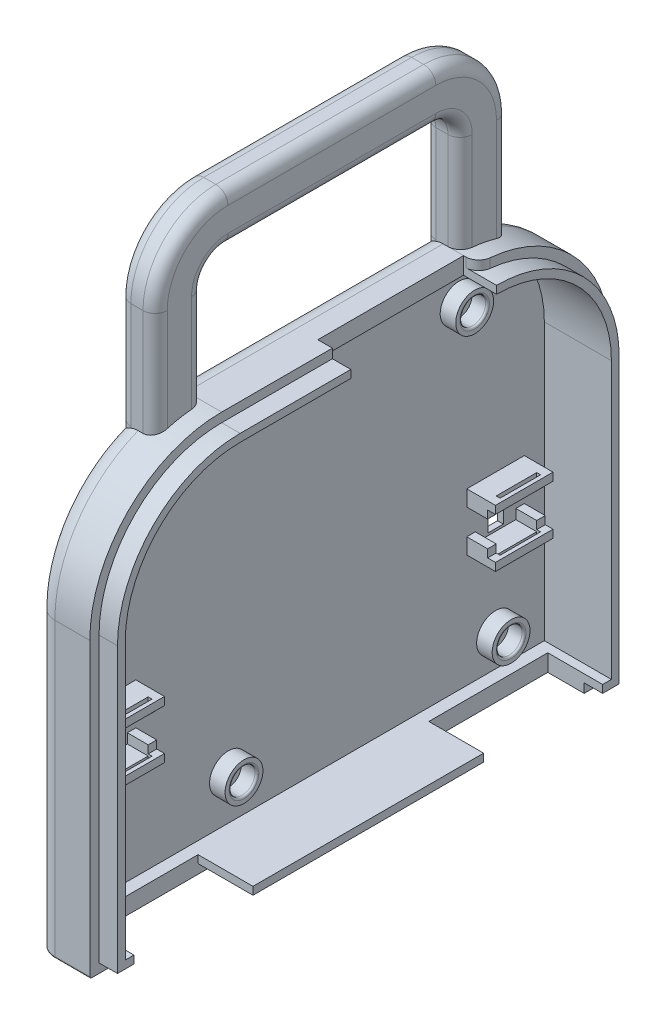
SolidWorks part; units mm, degrees
ref_plane "Front Plane" through (0, 0, 0) normal (0, 0, 1) x (1, 0, 0)
ref_plane "Top Plane" through (0, 0, 0) normal (0, 1, 0) x (1, 0, 0)
ref_plane "Right Plane" through (0, 0, 0) normal (1, 0, 0) x (0, 0, -1)
sketch "Sketch1" plane through (0, 0, 0) normal (1, 0, 0) x (0, 0, -1)
  line L0 (-52.8, 99.65) -> (52.8, 99.65)
  line L1 (-107.1, 45.35) -> (-107.1, -45.35)
  line L2 (-70, -75.35) -> (70, -75.35)
  line L3 (107.1, 45.35) -> (107.1, -45.35)
  line L4 (107.1, 0) -> (-107.1, 0) construction
  line L5 (0, 99.65) -> (0, -75.35) construction
  line L11 (107.1, -45.35) -> (107.1, -75.35)
  line L12 (107.1, -75.35) -> (70, -75.35)
  line L13 (-83.2, -1.7) -> (-76.8, -1.7)
  line L14 (-83.2, -1.7) -> (-83.2, -18.3)
  line L15 (-83.2, -18.3) -> (-76.8, -18.3)
  line L16 (-76.8, -1.7) -> (-76.8, -18.3)
  line L17 (-83.2, -1.7) -> (-76.8, -18.3) construction
  line L18 (-83.2, -18.3) -> (-76.8, -1.7) construction
  line L19 (76.8, -1.7) -> (83.2, -1.7)
  line L20 (76.8, -1.7) -> (76.8, -18.3)
  line L21 (76.8, -18.3) -> (83.2, -18.3)
  line L22 (83.2, -1.7) -> (83.2, -18.3)
  line L23 (76.8, -1.7) -> (83.2, -18.3) construction
  line L24 (76.8, -18.3) -> (83.2, -1.7) construction
  line L25 (80, -10) -> (-80, -10) construction
  line L27 (-107.1, -45.35) -> (-107.1, -75.35)
  line L28 (-107.1, -75.35) -> (-70, -75.35)
  arc A0 (52.8, 99.65) -> (107.1, 45.35) centre (52.8, 45.35) cw
  arc A1 (-52.8, 99.65) -> (-107.1, 45.35) centre (-52.8, 45.35) ccw
  point P16 (0, 0)
  point P17 (-80, -10)
  point P32 (80, -10)
  point P39 (-80, -10)
  point P40 (0, -10)
  dimension "D4" = 54.3
  dimension "D2" = 175
  dimension "D3" = 214.2
  dimension "D5" = 140
  dimension "D6" = 30
  dimension "D7" = 160
  dimension "D8" = 6.4
  dimension "D9" = 16.6
  dimension "D10" = 6.4
  dimension "D11" = 16.6
  dimension "D12" = 10
extrude "Boss-Extrude1" add sketch "Sketch1" along normal blind 2.4
sketch "Sketch9" plane through (2.4, 0, 0) normal (1, 0, 0) x (0, 0, -1)
  line L17 (52.8, 99.65) -> (-52.8, 99.65)
  line L31 (52.8, 99.65) -> (-52.8, 99.65)
  line L32 (-107.1, 45.35) -> (-107.1, -75.35)
  line L33 (-107.1, 45.35) -> (-107.1, -75.35)
  line L34 (-107.1, -75.35) -> (107.1, -75.35)
  line L39 (107.1, -75.35) -> (107.1, 45.35)
  line L43 (107.1, -75.35) -> (107.1, 45.35)
  line L45 (-107.1, -75.35) -> (107.1, -75.35)
  arc A15 (-52.8, 99.65) -> (-107.1, 45.35) centre (-52.8, 45.35) ccw
  arc A16 (-52.8, 99.65) -> (-107.1, 45.35) centre (-52.8, 45.35) ccw
  arc A17 (107.1, 45.35) -> (52.8, 99.65) centre (52.8, 45.35) ccw
  arc A18 (107.1, 45.35) -> (52.8, 99.65) centre (52.8, 45.35) ccw
  dimension "D1" = 0
sketch "Sketch10" plane through (2.4, 0, 0) normal (1, 0, 0) x (0, 0, -1)
  line L0 (65, -55.35) -> (0, -55.35) construction
  line L1 (-65, -55.35) -> (65, -55.35) construction
  line L2 (-65, -55.35) -> (-65, 54.65) construction
  line L3 (-65, 54.65) -> (65, 54.65) construction
  line L4 (65, -55.35) -> (65, 54.65) construction
  line L5 (-65, -55.35) -> (65, 54.65) construction
  line L6 (-65, 54.65) -> (65, -55.35) construction
  line L7 (0, -55.35) -> (-65, -55.35) construction
  line L8 (-107.1, -75.35) -> (107.1, -75.35) construction
  line L9 (0, -0.35) -> (0, 0) construction
  line L10 (0, -0.35) -> (0, -50.35) construction
  line L11 (-65, 54.65) -> (-65, 70.65) construction
  line L12 (-65, 70.65) -> (-70, 70.65) construction
  line L13 (0, -50.35) -> (-30, -50.35) construction
  circle A11 centre (-30, -50.35) radius 2.3
  circle A13 centre (65, 69.65) radius 2.3
  circle A14 centre (80, -55.35) radius 2.3
  circle A15 centre (-70, 70.65) radius 2.3
  point P0 (0, -0.35)
  point P11 (0, -55.35)
  point P12 (32.5, -55.35)
  point P14 (-32.5, -55.35)
  dimension "D3" = 15
  dimension "D4" = 20
  dimension "D8" = 4.6
  dimension "D1" = 130
  dimension "D2" = 110
  dimension "D5" = 50
  dimension "D6" = 15
  dimension "D7" = 16
  dimension "D9" = 5
  dimension "D10" = 30
extrude "Cut-Extrude1" cut sketch "Sketch10" against normal blind 100 and the other way blind 1000
sketch "Sketch12" plane through (2.4, 0, 0) normal (1, 0, 0) x (0, 0, -1)
  line L5 (-88.35, -18.3) -> (-88.35, -15.3)
  line L6 (-88.35, -18.3) -> (-88.35, -1.7) construction
  line L22 (71.65, -18.3) -> (71.65, -15.3)
  line L23 (71.65, -18.3) -> (71.65, -1.7) construction
  line L24 (71.65, -18.3) -> (88.35, -18.3) construction
  line L25 (88.35, -18.3) -> (88.35, -1.7) construction
  line L26 (71.65, -1.7) -> (88.35, -1.7) construction
  line L27 (71.65, -18.3) -> (88.35, -1.7) construction
  line L28 (88.35, -18.3) -> (71.65, -1.7) construction
  line L29 (71.65, -1.7) -> (71.65, -4.7)
  line L30 (88.35, -18.3) -> (88.35, -15.3)
  line L31 (88.35, -1.7) -> (88.35, -4.7)
  line L32 (71.65, -1.7) -> (88.35, -1.7) construction
  line L33 (88.35, -18.3) -> (71.65, -18.3) construction
  line L34 (88.35, -15.3) -> (91.85, -15.3)
  line L35 (71.65, -15.3) -> (68.15, -15.3)
  line L36 (68.15, -15.3) -> (68.15, -21.8)
  line L37 (68.15, -21.8) -> (91.85, -21.8)
  line L38 (91.85, -21.8) -> (91.85, -15.3)
  line L39 (71.65, -4.7) -> (68.15, -4.7)
  line L40 (68.15, -4.7) -> (68.15, 1.8)
  line L41 (68.15, 1.8) -> (91.85, 1.8)
  line L42 (91.85, 1.8) -> (91.85, -4.7)
  line L43 (91.85, -4.7) -> (88.35, -4.7)
  line L44 (83.2, -18.3) -> (76.8, -1.7) construction
  line L45 (83.2, -1.7) -> (76.8, -18.3) construction
  line L46 (-88.35, -18.3) -> (-71.65, -18.3) construction
  line L47 (-71.65, -18.3) -> (-71.65, -1.7) construction
  line L48 (-88.35, -1.7) -> (-71.65, -1.7) construction
  line L49 (-88.35, -18.3) -> (-71.65, -1.7) construction
  line L50 (-71.65, -18.3) -> (-88.35, -1.7) construction
  line L51 (-88.35, -1.7) -> (-88.35, -4.7)
  line L52 (-71.65, -18.3) -> (-71.65, -15.3)
  line L53 (-71.65, -1.7) -> (-71.65, -4.7)
  line L54 (-88.35, -1.7) -> (-71.65, -1.7) construction
  line L55 (-71.65, -18.3) -> (-88.35, -18.3) construction
  line L56 (-71.65, -15.3) -> (-68.15, -15.3)
  line L57 (-88.35, -15.3) -> (-91.85, -15.3)
  line L58 (-91.85, -15.3) -> (-91.85, -21.8)
  line L59 (-91.85, -21.8) -> (-68.15, -21.8)
  line L60 (-68.15, -21.8) -> (-68.15, -15.3)
  line L61 (-88.35, -4.7) -> (-91.85, -4.7)
  line L62 (-91.85, -4.7) -> (-91.85, 1.8)
  line L63 (-91.85, 1.8) -> (-68.15, 1.8)
  line L64 (-68.15, 1.8) -> (-68.15, -4.7)
  line L65 (-68.15, -4.7) -> (-71.65, -4.7)
  line L66 (-76.8, -18.3) -> (-83.2, -1.7) construction
  line L67 (-83.2, -18.3) -> (-76.8, -1.7) construction
  line L68 (-88.35, -1.7) -> (-88.35, -0.7047)
  line L69 (-88.35, -0.7047) -> (-71.65, -0.7047)
  line L70 (-71.65, -0.7047) -> (-71.65, -1.7)
  line L71 (-88.35, -18.3) -> (-88.35, -19.3)
  line L72 (-88.35, -19.3) -> (-71.65, -19.3)
  line L73 (-71.65, -19.3) -> (-71.65, -18.3)
  line L74 (88.35, -18.3) -> (88.35, -19.3)
  line L75 (88.35, -19.3) -> (71.65, -19.3)
  line L76 (71.65, -19.3) -> (71.65, -18.3)
  line L77 (88.35, -1.7) -> (88.35, -0.7047)
  line L78 (88.35, -0.7047) -> (71.65, -0.7047)
  line L79 (71.65, -0.7047) -> (71.65, -1.7)
  point P3 (-0.1438, 64.1533)
  point P4 (-80, -10)
  point P19 (80, -10)
  point P21 (-80, -10)
  point P30 (380.6447, 32.9453)
  point P31 (130.7088, -20.4974)
  point P32 (80, -10)
  point P49 (169.9078, -49.5925)
  dimension "D3" = 16.7
  dimension "D4" = 16.6
  dimension "D5" = 10.6
  dimension "D6" = 3.5
  dimension "D7" = 3.5
  dimension "D8" = 3.5
  dimension "D9" = 3.5
  dimension "D10" = 4.9497
  dimension "D11" = 16.7
  dimension "D12" = 16.6
  dimension "D13" = 10.6
  dimension "D14" = 3.5
  dimension "D15" = 3.5
  dimension "D16" = 3.5
  dimension "D17" = 3.5
  dimension "D18" = 4.9497
  dimension "D19" = 4.9497
  dimension "D20" = 7.3824
  dimension "D21" = 23.5468
  dimension "D22" = 24.088
  dimension "D23" = 4.9497
  dimension "D24" = 7.3824
  dimension "D25" = 23.5468
  dimension "D26" = 24.088
  dimension "D27" = 0.9953
  dimension "D28" = 1
  dimension "D29" = 1
  dimension "D30" = 0.9953
extrude "Boss-Extrude2" add sketch "Sketch12" along normal blind 8.6
sketch "Sketch14" plane through (11, 0, 0) normal (1, 0, 0) x (0, 0, -1)
  line L0 (-91.85, 1.8) -> (-91.85, -4.7) construction
  line L1 (-91.85, 1.8) -> (-68.15, 1.8)
  line L2 (-91.85, 1.8) -> (-91.85, -1.45)
  line L3 (-91.85, -1.45) -> (-68.15, -1.45)
  line L4 (-68.15, 1.8) -> (-68.15, -1.45)
  line L5 (-68.15, 1.8) -> (-91.85, 1.8) construction
  line L6 (-68.15, -4.7) -> (-68.15, 1.8) construction
  line L7 (-68.15, -21.8) -> (-68.15, -15.3) construction
  line L8 (-91.85, -21.8) -> (-68.15, -21.8)
  line L9 (-91.85, -21.8) -> (-91.85, -18.55)
  line L10 (-91.85, -18.55) -> (-68.15, -18.55)
  line L11 (-68.15, -21.8) -> (-68.15, -18.55)
  line L12 (91.85, -21.8) -> (91.85, -15.3) construction
  line L13 (68.15, -21.8) -> (91.85, -21.8)
  line L14 (68.15, -21.8) -> (68.15, -18.55)
  line L15 (68.15, -18.55) -> (91.85, -18.55)
  line L16 (91.85, -21.8) -> (91.85, -18.55)
  line L17 (91.85, -4.7) -> (91.85, 1.8) construction
  line L18 (68.15, 1.8) -> (91.85, 1.8)
  line L19 (68.15, 1.8) -> (68.15, -1.45)
  line L20 (68.15, -1.45) -> (91.85, -1.45)
  line L21 (91.85, 1.8) -> (91.85, -1.45)
extrude "Boss-Extrude3" add sketch "Sketch14" along normal blind 3.2
sketch "Sketch17" plane through (0, 0, 0) normal (1, 0, 0) x (0, 0, -1)
  line L0 (-103.9, 45.35) -> (-103.9, -72.15) construction
  line L1 (-103.9, -72.15) -> (103.9, -72.15) construction
  line L2 (103.9, -72.15) -> (103.9, 45.35) construction
  line L3 (52.8, 96.45) -> (-52.8, 96.45) construction
  line L4 (52.8, 99.65) -> (-52.8, 99.65)
  line L5 (-107.1, 45.35) -> (-107.1, -75.35)
  line L6 (-107.1, -75.35) -> (107.1, -75.35)
  line L7 (107.1, -75.35) -> (107.1, 45.35)
  line L8 (52.8, 99.65) -> (-52.8, 99.65) construction
  line L9 (-107.1, 45.35) -> (-107.1, -75.35) construction
  line L11 (107.1, -75.35) -> (107.1, 45.35) construction
  line L16 (100.1, -68.35) -> (100.1, 45.35)
  line L17 (52.8, 92.65) -> (-52.8, 92.65)
  line L18 (-100.1, 45.35) -> (-100.1, -68.35)
  line L19 (-100.1, -68.35) -> (100.1, -68.35)
  line L24 (52.8, 95.85) -> (-52.8, 95.85)
  line L25 (-103.3, 45.35) -> (-103.3, -71.55)
  line L27 (103.3, -71.55) -> (103.3, 45.35)
  line L28 (-107.1, -75.35) -> (107.1, -75.35) construction
  line L29 (-103.3, -71.55) -> (103.3, -71.55) construction
  line L31 (-103.3, -71.55) -> (103.3, -71.55)
  arc A0 (103.9, 45.35) -> (52.8, 96.45) centre (52.8, 45.35) ccw construction
  arc A1 (-52.8, 96.45) -> (-103.9, 45.35) centre (-52.8, 45.35) ccw construction
  arc A2 (-52.8, 99.65) -> (-107.1, 45.35) centre (-52.8, 45.35) ccw
  arc A3 (107.1, 45.35) -> (52.8, 99.65) centre (52.8, 45.35) ccw
  arc A4 (-52.8, 99.65) -> (-107.1, 45.35) centre (-52.8, 45.35) ccw construction
  arc A5 (107.1, 45.35) -> (52.8, 99.65) centre (52.8, 45.35) ccw construction
  arc A8 (100.1, 45.35) -> (52.8, 92.65) centre (52.8, 45.35) ccw
  arc A9 (-52.8, 92.65) -> (-100.1, 45.35) centre (-52.8, 45.35) ccw
  arc A12 (-52.8, 95.85) -> (-103.3, 45.35) centre (-52.8, 45.35) ccw
  arc A13 (103.3, 45.35) -> (52.8, 95.85) centre (52.8, 45.35) ccw
  dimension "D4" = 167.4
  dimension "D5" = 206.6
  dimension "D7" = 207.8
  dimension "D8" = 214.2
  dimension "D9" = 3.2
  dimension "D2" = 3.2
  dimension "D10" = 3.2
  dimension "D11" = 3.2
  dimension "D1" = 0
  dimension "D3" = 3.2
  dimension "D6" = 0.6
extrude "Boss-Extrude4" add sketch "Sketch17" along normal blind 30
sketch "Sketch21" plane through (2.4, 0, 0) normal (1, 0, 0) x (0, 0, -1)
  line L4 (-107.1, -75.35) -> (107.1, -75.35)
  line L6 (-107.1, -75.35) -> (107.1, -75.35)
  line L8 (52.8, 99.65) -> (-52.8, 99.65)
  line L9 (-107.1, 45.35) -> (-107.1, -75.35)
  line L11 (107.1, -75.35) -> (107.1, 45.35)
  line L12 (52.8, 99.65) -> (-52.8, 99.65)
  line L13 (-107.1, 45.35) -> (-107.1, -75.35)
  line L15 (107.1, -75.35) -> (107.1, 45.35)
  arc A4 (-52.8, 99.65) -> (-107.1, 45.35) centre (-52.8, 45.35) ccw
  arc A5 (107.1, 45.35) -> (52.8, 99.65) centre (52.8, 45.35) ccw
  arc A6 (-52.8, 99.65) -> (-107.1, 45.35) centre (-52.8, 45.35) ccw
  arc A7 (107.1, 45.35) -> (52.8, 99.65) centre (52.8, 45.35) ccw
  dimension "D1" = 0
sketch "Sketch22" plane through (2.4, 0, 0) normal (1, 0, 0) x (0, 0, -1)
  line L0 (-107.1, -75.35) -> (107.1, -75.35) construction
  line L1 (-107.1, -75.35) -> (107.1, -75.35)
  line L21 (52.8, 99.65) -> (-52.8, 99.65)
  line L22 (107.1, -75.35) -> (107.1, 45.35)
  line L24 (-107.1, 45.35) -> (-107.1, -75.35)
  line L25 (52.8, 99.65) -> (-52.8, 99.65)
  line L26 (107.1, -75.35) -> (107.1, 45.35)
  line L28 (-107.1, 45.35) -> (-107.1, -75.35)
  line L44 (-103.3, -71.55) -> (103.3, -71.55)
  line L45 (103.3, -71.55) -> (103.3, 45.35)
  line L46 (52.8, 95.85) -> (-52.8, 95.85)
  line L47 (-103.3, 45.35) -> (-103.3, -71.55)
  line L48 (-103.3, -71.55) -> (103.3, -71.55)
  line L49 (103.3, -71.55) -> (103.3, 45.35)
  line L50 (52.8, 95.85) -> (-52.8, 95.85)
  line L51 (-103.3, 45.35) -> (-103.3, -71.55)
  arc A6 (-52.8, 99.65) -> (-107.1, 45.35) centre (-52.8, 45.35) ccw
  arc A7 (107.1, 45.35) -> (52.8, 99.65) centre (52.8, 45.35) ccw
  arc A8 (-52.8, 99.65) -> (-107.1, 45.35) centre (-52.8, 45.35) ccw
  arc A9 (107.1, 45.35) -> (52.8, 99.65) centre (52.8, 45.35) ccw
  arc A20 (103.3, 45.35) -> (52.8, 95.85) centre (52.8, 45.35) ccw
  arc A21 (-52.8, 95.85) -> (-103.3, 45.35) centre (-52.8, 45.35) ccw
  arc A22 (103.3, 45.35) -> (52.8, 95.85) centre (52.8, 45.35) ccw
  arc A23 (-52.8, 95.85) -> (-103.3, 45.35) centre (-52.8, 45.35) ccw
  dimension "D1" = 0
  dimension "D2" = 0
extrude "Boss-Extrude7" add sketch "Sketch22" along normal blind 20
sketch "Sketch23" plane through (0, -75.35, 0) normal (0, -1, 0) x (1, 0, 0)
  line L0 (0, 99.1) -> (0, 107.1)
  line L1 (0, 107.1) -> (8, 107.1)
  line L2 (8, -107.1) -> (0, -107.1)
  line L3 (0, -107.1) -> (0, -99.1)
  line L8 (0, 107.1) -> (0, -107.1)
  line L9 (0, -107.1) -> (22.4, -107.1)
  line L10 (22.4, -107.1) -> (22.4, 107.1)
  line L11 (22.4, 107.1) -> (0, 107.1)
  line L12 (0, 99.1) -> (0, -99.1) construction
  line L13 (8, -107.1) -> (22.4, -107.1) construction
  line L15 (22.4, 107.1) -> (8, 107.1) construction
  arc A0 (0, 99.1) -> (8, 107.1) centre (8, 99.1) cw
  arc A1 (0, -99.1) -> (8, -107.1) centre (8, -99.1) ccw
  dimension "D2" = 8
  dimension "D1" = 0
extrude "Cut-Extrude4" cut sketch "Sketch23" against normal through all
fillet "Fillet4" radius 8 3 edges at (0, 92.7258, 79.3335) (0, 99.65, 0) (0, 92.7258, -79.3335)
sketch "Sketch26" plane through (22.4, 0, 0) normal (1, 0, 0) x (0, 0, -1)
  line L1 (-47.5, -68.3365) -> (47.5, -68.3365)
  line L2 (47.5, -68.3365) -> (47.5, -71.55)
  line L6 (47.5, -71.55) -> (-47.5, -71.55)
  line L7 (-47.5, -71.55) -> (-47.5, -68.3365)
  line L8 (-103.3, -71.55) -> (103.3, -71.55) construction
  line L9 (-96.5, -79.5369) -> (96.5, -79.5369)
  line L10 (-96.5, -79.5369) -> (-96.5, -63.5631)
  line L11 (-96.5, -63.5631) -> (96.5, -63.5631)
  line L12 (96.5, -79.5369) -> (96.5, -63.5631)
  line L13 (-96.5, -79.5369) -> (96.5, -63.5631) construction
  line L14 (-96.5, -63.5631) -> (96.5, -79.5369) construction
  line L15 (107.1, -75.35) -> (107.1, 45.35) construction
  point P0 (0, -71.55)
  point P9 (0, -68.3365)
  point P13 (0, -68.3365)
  point P16 (0, -68.3365)
  dimension "D1" = 10.6
  dimension "D2" = 15.9739
  dimension "D3" = 95
  dimension "D4" = 3.2135
extrude "Cut-Extrude7" cut sketch "Sketch26" against normal blind 15 and the other way blind 20
sketch "Sketch28" plane through (0, 99.65, 0) normal (0, 1, 0) x (1, 0, 0)
  line L0 (22.4, 52.8) -> (16.4, 52.8)
  line L1 (22.4, 52.8) -> (8, 52.8) construction
  line L2 (16.4, 52.8) -> (16.4, -7.2)
  line L3 (16.4, -7.2) -> (51.1003, -7.2)
  line L4 (51.1003, -7.2) -> (51.1003, 52.8)
  line L5 (51.1003, 52.8) -> (22.4, 52.8)
  dimension "D1" = 6
  dimension "D2" = 60
extrude "Cut-Extrude8" cut sketch "Sketch28" against normal blind 10
sketch "Sketch29" plane through (0, -1.45, 0) normal (0, -1, 0) x (1, 0, 0)
  line L12 (11, -88.35) -> (11, -91.85) construction
  line L13 (11, -82.1) -> (11, -98.1)
  line L14 (11, -98.1) -> (12.5, -98.1)
  line L15 (12.5, -98.1) -> (12.5, -82.1)
  line L16 (12.5, -82.1) -> (11, -82.1)
  line L23 (2.4, 68.15) -> (14.2, 68.15)
  line L24 (2.4, 91.85) -> (2.4, 68.15)
  line L25 (14.2, 91.85) -> (2.4, 91.85)
  line L26 (14.2, 68.15) -> (14.2, 91.85)
  line L31 (2.4, 68.15) -> (14.2, 68.15) construction
  line L32 (2.4, 91.85) -> (2.4, 68.15) construction
  line L33 (14.2, 91.85) -> (2.4, 91.85) construction
  line L34 (14.2, 68.15) -> (14.2, 91.85) construction
  point P1 (11, -90.1)
  point P9 (11, -90.1)
  point P14 (11, -90.1)
  dimension "D1" = 0
  dimension "D3" = 16
  dimension "D4" = 1.5
sketch "Sketch30" plane through (2.4, 0, 0) normal (1, 0, 0) x (0, 0, -1)
  circle A0 centre (-70, 70.65) radius 5.3
  circle A1 centre (65, 69.65) radius 5.3
  circle A2 centre (-30, -50.35) radius 5.3
  circle A3 centre (80, -55.35) radius 5.3
  circle A5 centre (65, 69.65) radius 7.8
  circle A6 centre (80, -55.35) radius 7.8
  circle A7 centre (-30, -50.35) radius 7.8
  circle A8 centre (-70, 70.65) radius 7.8
  dimension "D1" = 10.6
  dimension "D2" = 15.6
extrude "Boss-Extrude8" add sketch "Sketch30" along normal blind 6.4
fillet "Fillet7" radius 0.8 4 edges at (8.8, -55.35, -85.3) (8.8, -50.35, 24.7) (8.8, 69.65, -70.3) (8.8, 70.65, 64.7)
fillet "Fillet8" radius 0.8 5 edges at (15.2, -75.35, 107.1) (2.3431, -75.35, 104.7569) (15.2, -75.35, -107.1) (2.3431, -75.35, -104.7569) (0, -75.35, 0)
sketch "Sketch31" plane through (0, 0, 0) normal (1, 0, 0) x (0, 0, -1)
  line L0 (-52.8, 99.65) -> (-52.8, 139.65)
  line L1 (-42.8, 149.65) -> (42.8, 149.65)
  line L2 (52.8, 139.65) -> (52.8, 99.65)
  line L3 (52.8, 99.65) -> (-52.8, 99.65) construction
  line L4 (-72.8, 95.8326) -> (-72.8, 139.65)
  line L5 (-42.8, 169.65) -> (42.8, 169.65)
  line L6 (72.8, 139.65) -> (72.8, 95.8326)
  arc A2 (-52.8, 99.65) -> (-107.1, 45.35) centre (-52.8, 45.35) ccw construction
  arc A3 (107.1, 45.35) -> (52.8, 99.65) centre (52.8, 45.35) ccw construction
  arc A4 (-52.8, 99.65) -> (-72.8, 95.8326) centre (-52.8, 45.35) ccw
  arc A5 (72.8, 95.8326) -> (52.8, 99.65) centre (52.8, 45.35) ccw
  arc A9 (-52.8, 139.65) -> (-42.8, 149.65) centre (-42.8, 139.65) cw
  arc A10 (42.8, 149.65) -> (52.8, 139.65) centre (42.8, 139.65) cw
  arc A11 (72.8, 139.65) -> (42.8, 169.65) centre (42.8, 139.65) ccw
  arc A12 (-42.8, 169.65) -> (-72.8, 139.65) centre (-42.8, 139.65) ccw
  point P13 (52.8, 149.65)
  dimension "D2" = 10
  dimension "D1" = 50
  dimension "D3" = 20
  dimension "D4" = 20
extrude "Boss-Extrude9" add sketch "Sketch31" along normal blind 15
fillet "Fillet9" radius 5 21 edges at (22.4, 97.75, -52.8) (0, 117.7413, -72.8) (0, 160.8632, -64.0132) (0, 117.7413, 72.8) (0, 160.8632, 64.0132) (0, 119.65, 52.8) (0, 146.7211, 49.8711) (0, 149.65, 0) (0, 146.7211, -49.8711) (15, 119.65, 52.8) (15, 119.65, -52.8) (15, 146.7211, -49.8711) (15, 149.65, 0) (15, 117.7413, -72.8) (15, 160.8632, -64.0132) (15, 169.65, 0) (15, 117.7413, 72.8) (0, 169.65, 0) (0, 119.65, -52.8) (15, 146.7211, 49.8711) (15, 160.8632, 64.0132)
sketch "Sketch32" plane through (0, 0, 0) normal (-1, 0, 0) x (0, 0, 1)
  line L0 (52.8, 99.65) -> (52.8, 91.65)
  line L1 (72.8, 95.8326) -> (72.8, 87.1075)
  line L2 (-72.8, 95.8326) -> (-72.8, 87.1075)
  line L3 (-52.8, 99.65) -> (-52.8, 91.65)
  arc A0 (67.8, 97.5371) -> (57.8, 99.4193) centre (52.8, 45.35) ccw construction
  arc A1 (-52.8, 91.65) -> (-99.1, 45.35) centre (-52.8, 45.35) ccw construction
  arc A2 (-52.8, 99.65) -> (-57.8, 99.4193) centre (-52.8, 45.35) ccw construction
  arc A3 (-57.8, 99.4193) -> (-67.8, 97.5371) centre (-52.8, 45.35) ccw construction
  arc A4 (-67.8, 97.5371) -> (-72.8, 95.8326) centre (-52.8, 45.35) ccw construction
  arc A5 (72.8, 95.8326) -> (67.8, 97.5371) centre (52.8, 45.35) ccw construction
  arc A6 (57.8, 99.4193) -> (52.8, 99.65) centre (52.8, 45.35) ccw construction
  arc A7 (99.1, 45.35) -> (52.8, 91.65) centre (52.8, 45.35) ccw construction
  arc A8 (67.8, 97.5371) -> (57.8, 99.4193) centre (52.8, 45.35) ccw
  arc A9 (-52.8, 91.65) -> (-72.8, 87.1075) centre (-52.8, 45.35) ccw
  arc A10 (-52.8, 99.65) -> (-57.8, 99.4193) centre (-52.8, 45.35) ccw
  arc A11 (-57.8, 99.4193) -> (-67.8, 97.5371) centre (-52.8, 45.35) ccw
  arc A12 (-67.8, 97.5371) -> (-72.8, 95.8326) centre (-52.8, 45.35) ccw
  arc A13 (72.8, 95.8326) -> (67.8, 97.5371) centre (52.8, 45.35) ccw
  arc A14 (57.8, 99.4193) -> (52.8, 99.65) centre (52.8, 45.35) ccw
  arc A15 (72.8, 87.1075) -> (52.8, 91.65) centre (52.8, 45.35) ccw
extrude "Boss-Extrude10" add sketch "Sketch32" against normal up to body separate body
fillet "Fillet10" radius 5 4 edges at (0, 91.47, 72.8) (0, 95.65, 52.8) (0, 95.65, -52.8) (0, 91.47, -72.8)
sketch "Sketch33" plane through (0, -18.55, 0) normal (0, 1, 0) x (1, 0, 0)
  line L0 (11, 91.85) -> (11, 88.35) construction
  line L1 (11, 88.35) -> (11, 71.65) construction
  line L2 (11, 71.65) -> (11, 68.15) construction
  line L3 (11, 68.15) -> (14.2, 68.15) construction
  line L4 (14.2, 68.15) -> (14.2, 91.85) construction
  line L5 (14.2, 91.85) -> (11, 91.85) construction
  line L6 (11, -68.15) -> (11, -71.65) construction
  line L7 (11, -71.65) -> (11, -88.35) construction
  line L8 (11, -88.35) -> (11, -91.85) construction
  line L9 (11, -91.85) -> (14.2, -91.85) construction
  line L10 (14.2, -91.85) -> (14.2, -68.15) construction
  line L11 (14.2, -68.15) -> (11, -68.15) construction
  line L12 (11, 91.85) -> (11, 88.35) construction
  line L13 (11, 88.35) -> (11, 71.65)
  line L14 (11, 71.65) -> (11, 68.15) construction
  line L15 (11, 68.15) -> (14.2, 68.15) construction
  line L16 (14.2, 68.15) -> (14.2, 91.85) construction
  line L17 (14.2, 91.85) -> (11, 91.85) construction
  line L18 (11, -68.15) -> (11, -71.65) construction
  line L19 (11, -71.65) -> (11, -88.35)
  line L20 (11, -88.35) -> (11, -91.85) construction
  line L21 (11, -91.85) -> (14.2, -91.85) construction
  line L22 (14.2, -91.85) -> (14.2, -68.15) construction
  line L23 (14.2, -68.15) -> (11, -68.15) construction
  line L24 (11, -88.35) -> (12.6001, -88.35)
  line L25 (12.6001, -88.35) -> (12.6001, -71.65)
  line L26 (12.6001, -71.65) -> (11, -71.65)
  line L27 (11, 71.65) -> (12.6001, 71.65)
  line L28 (12.6001, 71.65) -> (12.6001, 88.35)
  line L29 (12.6001, 88.35) -> (11, 88.35)
  dimension "D1" = 1.6001
  dimension "D2" = 1.6001
extrude "Cut-Extrude9" cut sketch "Sketch33" against normal up to surface and the other way up to surface up to face at (8.3, -21.8, -80) other way up to face at (8.3, 1.8, -80)
